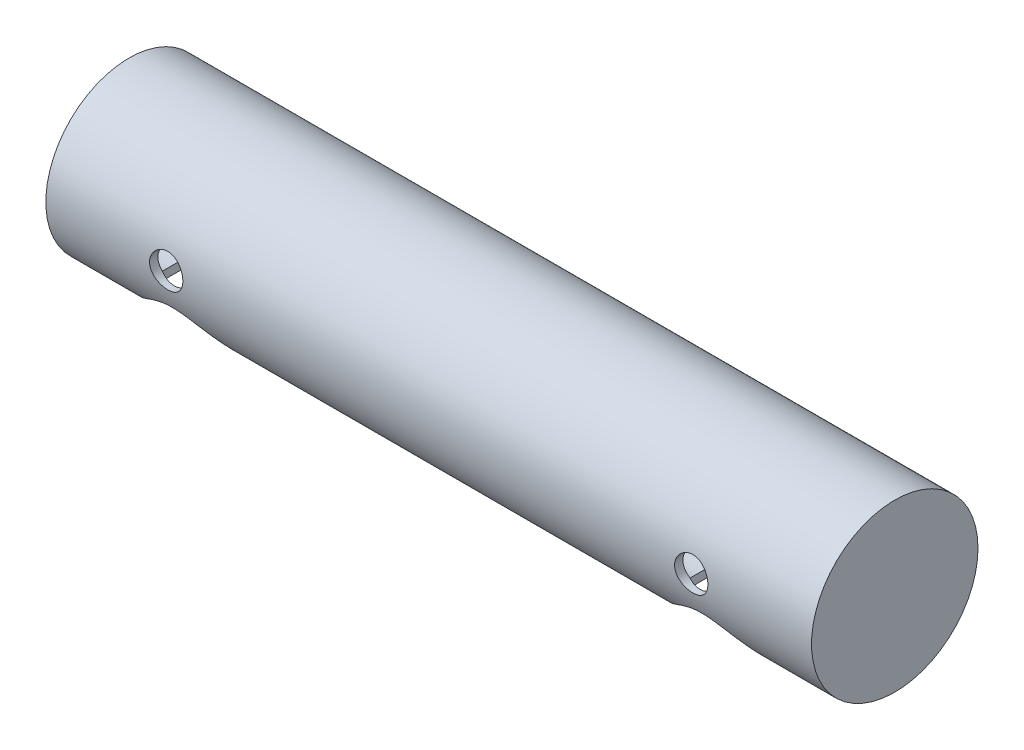
SolidWorks part; units mm, degrees
ref_plane "Front Plane" through (0, 0, 0) normal (0, 0, 1) x (1, 0, 0)
ref_plane "Top Plane" through (0, 0, 0) normal (0, 1, 0) x (1, 0, 0)
ref_plane "Right Plane" through (0, 0, 0) normal (1, 0, 0) x (0, 0, -1)
sketch "Sketch1" plane through (0, 0, 0) normal (1, 0, 0) x (0, 0, -1)
  circle A0 centre (0, 0) radius 50
  dimension "D1" = 100
extrude "Boss-Extrude1" add sketch "Sketch1" along normal blind 420 and the other way blind 40
shell "Shell12" thickness 5
sketch "Sketch2" plane through (0, 0, 0) normal (0, 1, 0) x (1, 0, 0)
  circle A0 centre (349.0779, 0) radius 45
  dimension "D1" = 90
ref_plane "Plane2" through (190, 0, 0) normal (1, 0, 0) x (0, 0, -1)
extrude "Cut-Extrude2" cut sketch "Sketch2" against normal blind 50
sketch "Sketch4" plane through (0, 0, 0) normal (0, 0, 1) x (1, 0, 0)
  line L0 (394.0779, 0) -> (304.0779, 0) construction
  circle A0 centre (347.7064, 0) radius 10
  dimension "D1" = 20
extrude "Cut-Extrude3" cut sketch "Sketch4" against normal blind 50 and the other way blind 50
mirror "Mirror1" about plane through (190, 0, 0) normal (1, 0, 0) of "Cut-Extrude3", "Cut-Extrude2"
